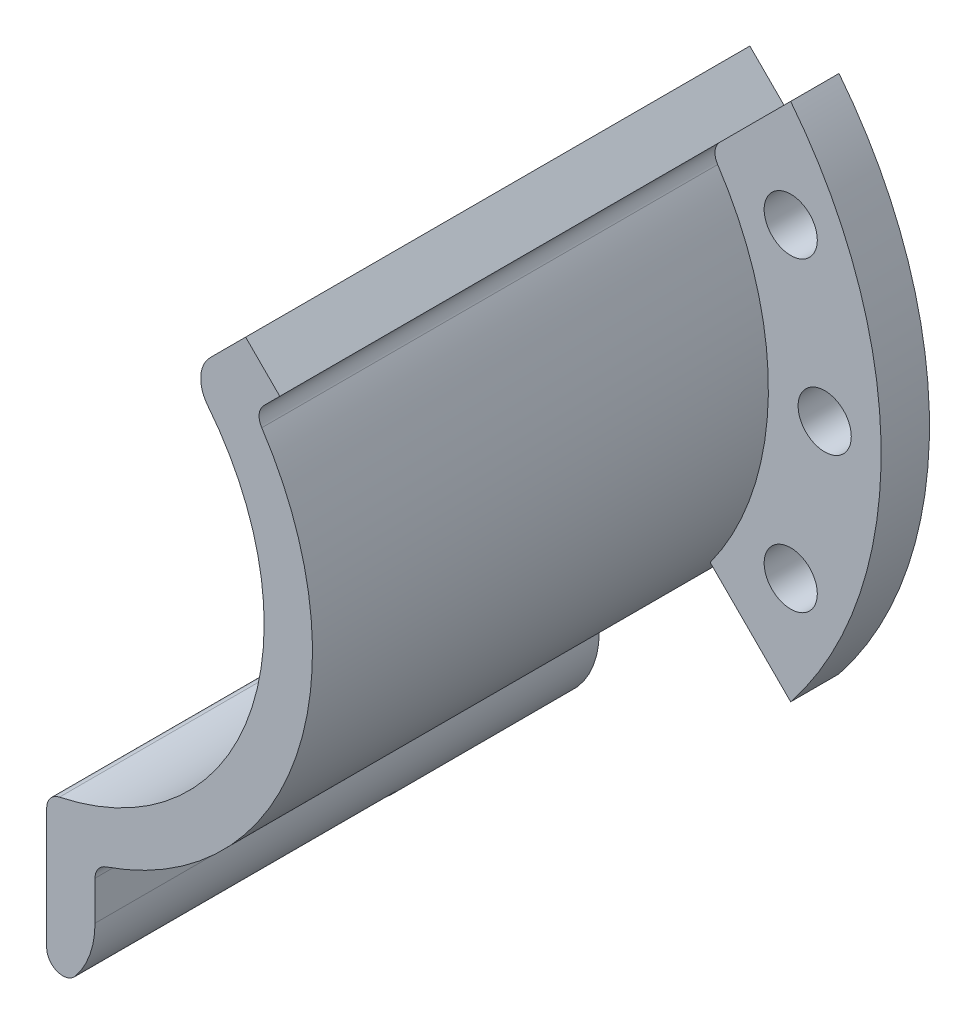
SolidWorks part; units mm, degrees
ref_plane "前视基准面" through (0, 0, 0) normal (0, 0, 1) x (1, 0, 0)
ref_plane "上视基准面" through (0, 0, 0) normal (0, 1, 0) x (1, 0, 0)
ref_plane "右视基准面" through (0, 0, 0) normal (1, 0, 0) x (0, 0, -1)
sketch "草图1" plane through (0, 0, -1.3) normal (0, 0, 1) x (1, 0, 0)
  line L0 (14.8492, 14.8492) -> (11.3137, 11.3137)
  line L1 (0, 23.564) -> (0, -22.8784) construction
  line L2 (11.3137, 11.3137) -> (36.0624, 36.0624) construction
  line L3 (2.5, -15.8035) -> (2.5, -18.8348)
  line L4 (1.5, -13.5) -> (1.5, -14.3614) construction
  line L5 (14.8492, 14.8492) -> (16.9706, 12.7279)
  line L6 (16.9706, 12.7279) -> (15.3878, 11.1452)
  arc A0 (11.9682, -9.0422) -> (14.8566, -2.069) centre (0, 0) ccw construction
  arc A2 (2.5, -18.8348) -> (15.3878, 11.1452) centre (0, 0) ccw
  arc A3 (2.5, -15.8035) -> (11.3137, 11.3137) centre (0, 0) ccw
  point P20 (1.5, -13.9307)
  dimension "D1" = 1
  dimension "D4" = 45
  dimension "D2" = 3
  dimension "D3" = 5
  dimension "D5" = 1
  dimension "D6" = 3
  dimension "D7" = 35
extrude "凸台-拉伸1" add sketch "草图1" along normal up to surface (31.3 mm away)
sketch "草图2" plane through (0, 0, -1.3) normal (0, 0, 1) x (1, 0, 0)
  line L0 (15.3878, 11.1452) -> (16.9706, 12.7279) construction
  line L1 (0, 0) -> (31.8729, 0) construction
  line L2 (15.3878, 11.1452) -> (16.9706, 12.7279) construction
  line L3 (15.3878, 11.1452) -> (20.3833, 16.1407)
  line L4 (15.3878, -11.1452) -> (20.3833, -16.1407)
  arc A0 (20.3833, 16.1407) -> (20.3833, -16.1407) centre (0, 0) cw
  arc A2 (2.5, -18.8348) -> (15.3878, 11.1452) centre (0, 0) ccw construction
  arc A3 (15.3878, -11.1452) -> (15.3878, 11.1452) centre (0, 0) ccw
  arc A4 (17.8856, -13.6429) -> (17.8856, 13.6429) centre (0, 0) ccw construction
  dimension "D1" = 26
extrude "凸台-拉伸2" add sketch "草图2" along normal blind 3
sketch "草图8" plane through (0, 0, -1.3) normal (0, 0, 1) x (1, 0, 0)
  line L0 (2.5, -18.8348) -> (2.5, -21.3348)
  line L1 (0, -23.8348) -> (0, -26.8348)
  line L2 (5.5, -21.3348) -> (5.5, -18.1865)
  line L3 (2.5, -21.3348) -> (-1.9026, -21.3348) construction
  line L4 (0, -23.8348) -> (0, -21.3348) construction
  arc A0 (2.5, -21.3348) -> (0, -23.8348) centre (0, -21.3348) cw
  arc A1 (0, -26.8348) -> (5.5, -21.3348) centre (0, -21.3348) ccw
  arc A2 (2.5, -18.8348) -> (15.3878, 11.1452) centre (0, 0) ccw construction
  arc A4 (2.5, -18.8348) -> (15.3878, -11.1452) centre (0, 0) ccw construction
  arc A5 (2.5, -18.8348) -> (5.5, -18.1865) centre (0, 0) ccw
  dimension "D1" = 3
  dimension "D4" = 2.5
  dimension "D2" = 3
  dimension "D3" = 2.5
extrude "凸台-拉伸3" add sketch "草图8" along normal up to surface (31.3 mm away) up to face at (13.3904, 1.5063, 30)
sketch "草图9" plane through (0, 0, 30) normal (0, 0, 1) x (1, 0, 0)
  line L0 (2.5, -15.8035) -> (2.5, -21.3348) construction
  line L1 (-5.2306, -21.3348) -> (2.5, -21.3348)
  line L2 (-5.2306, -21.3348) -> (-5.2306, -27.3309)
  line L3 (-5.2306, -27.3309) -> (2.5, -27.3309)
  line L4 (2.5, -21.3348) -> (2.5, -27.3309)
extrude "切除-拉伸1" cut sketch "草图9" against normal blind 20
hole_wizard "ST2.9 间隙孔1" positions "草图6" profile "草图7" hole size "ST2.9" standard "GB" end condition through all
sketch "草图6" plane through (0, 0, 1.7) normal (0, 0, 1) x (1, 0, 0)
  line L0 (15.3878, -11.1452) -> (20.3833, -16.1407) construction
  line L1 (15.3878, 11.1452) -> (16.9706, 12.7279) construction
  line L2 (0, 0) -> (22.4949, 0) construction
  line L4 (0, 0) -> (20.3873, 9.5068) construction
  line L6 (0, 0) -> (20.3873, -9.5068) construction
  arc A0 (17.8856, -13.6429) -> (17.8856, 13.6429) centre (0, 0) ccw construction
  point P0 (22.4949, 0)
  point P14 (20.3873, 9.5068)
  point P16 (20.3873, -9.5068)
  dimension "D1" = 25
  dimension "D2" = 25
sketch "草图7" plane through (22.4949, 0, 1.7) normal (1, 0, 0) x (0, -1, 0)
  line L0 (0, 0) -> (0, 3)
  line L1 (0, 3) -> (1.65, 3)
  line L2 (1.65, 3) -> (1.65, 0)
  line L5 (1.65, 0) -> (0, 0)
  line L11 (0, -6.35) -> (0, 107.95) construction
  dimension "通孔孔直径" = 3.3
  dimension "通孔孔深度" = 3
fillet "圆角1" radius 1 4 edges at (2.5, -15.8035, 14.35) (15.3878, 11.1452, 15.85) (5.5, -18.1865, 14.35) (2.5, -26.2338, 20)
fillet "圆角2" radius 2 1 edges at (11.3137, 11.3137, 14.35)
